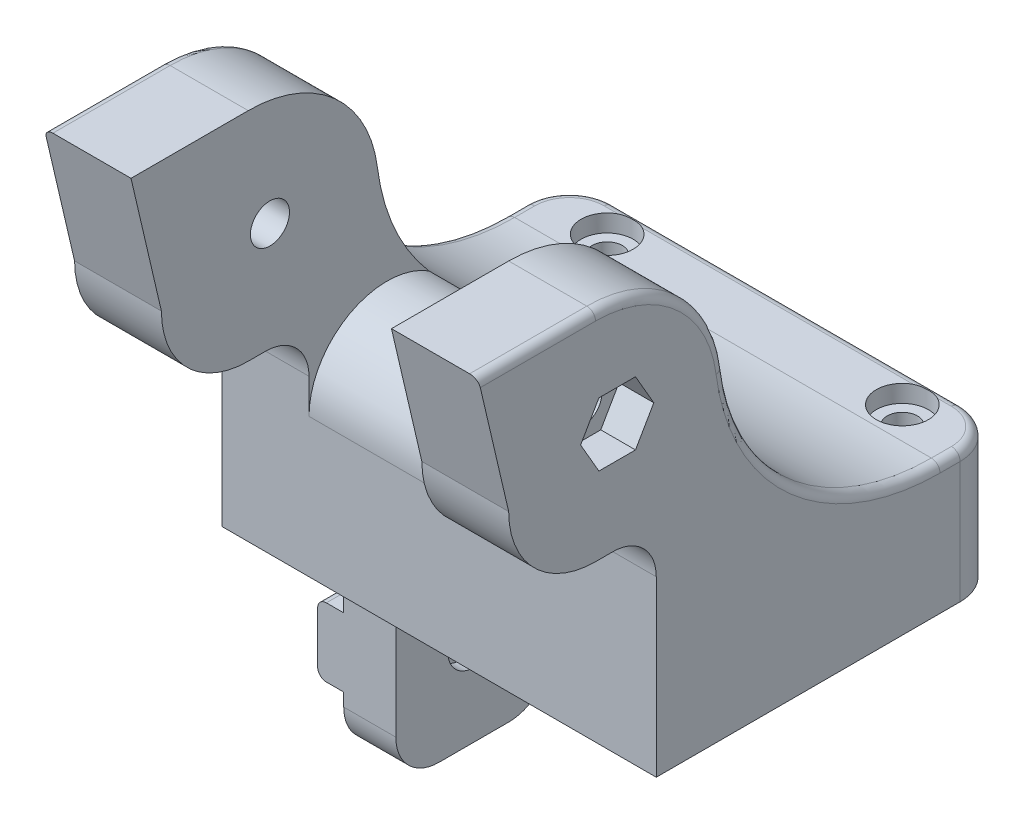
SolidWorks part; units mm, degrees
ref_plane "Alzado" through (0, 0, 0) normal (0, 0, 1) x (1, 0, 0)
ref_plane "Planta" through (0, 0, 0) normal (0, 1, 0) x (1, 0, 0)
ref_plane "Vista lateral" through (0, 0, 0) normal (1, 0, 0) x (0, 0, -1)
sketch "Croquis1" plane through (0, 0, 0) normal (0, 1, 0) x (1, 0, 0)
  line L1 (0, 0) -> (50, 0)
  line L2 (0, 0) -> (0, 40)
  line L3 (0, 40) -> (50, 40)
  line L4 (50, 0) -> (50, 40)
  dimension "D1" = 50
  dimension "D2" = 40
extrude "Saliente-Extruir1" add sketch "Croquis1" along normal blind 25
sketch "Croquis4" plane through (0, 25, 0) normal (0, 1, 0) x (1, 0, 0)
  line L0 (0, 40) -> (0, 0) construction
  line L1 (0, 8) -> (10, 8)
  line L2 (0, 8) -> (0, -17)
  line L3 (0, -17) -> (10, -17)
  line L4 (10, 8) -> (10, -17)
  line L5 (50, 0) -> (50, 40) construction
  line L6 (50, 8) -> (40, 8)
  line L7 (50, 8) -> (50, -17)
  line L8 (50, -17) -> (40, -17)
  line L9 (40, 8) -> (40, -17)
  line L10 (50, 40) -> (0, 40) construction
  dimension "D1" = 10
  dimension "D2" = 10
  dimension "D3" = 25
  dimension "D4" = 25
  dimension "D5" = 32
  dimension "D6" = 32
extrude "Saliente-Extruir3" add sketch "Croquis4" along normal blind 25
sketch "Croquis5" plane through (50, 0, 0) normal (1, 0, 0) x (0, 0, -1)
  line L0 (8, 50) -> (-17, 25) construction
  circle A0 centre (-4.5, 37.5) radius 2.25
  dimension "D1" = 4.5
extrude "Cortar-Extruir2" cut sketch "Croquis5" against normal up to surface (50 mm away) up to face at (0, 25, -7.75)
fillet "Redondeo4" radius 15 2 edges at (5, 50, -8) (45, 50, -8)
fillet "Redondeo5" radius 10 2 edges at (5, 25, 17) (45, 25, 17)
fillet "Redondeo6" radius 9 1 edges at (25, 25, 0)
sketch "Croquis6" plane through (0, 25, 0) normal (0, 1, 0) x (1, 0, 0)
  line L4 (0, 40) -> (0, 9)
  line L5 (0, 9) -> (50, 9)
  line L6 (50, 9) -> (50, 40)
  line L7 (50, 40) -> (0, 40)
  line L8 (0, 40) -> (0, 9)
  line L9 (0, 9) -> (50, 9)
  line L10 (50, 9) -> (50, 40)
  line L11 (50, 40) -> (0, 40)
  dimension "D1" = 0
extrude "Cortar-Extruir3" cut sketch "Croquis6" against normal blind 10
sketch "Croquis7" plane through (0, 0, -9) normal (0, 0, -1) x (-1, 0, 0)
  line L4 (0, 25) -> (-50, 25)
  line L5 (-50, 25) -> (-50, 15)
  line L6 (-50, 15) -> (0, 15)
  line L7 (0, 15) -> (0, 25)
  line L8 (0, 25) -> (-50, 25)
  line L9 (-50, 25) -> (-50, 15)
  line L10 (-50, 15) -> (0, 15)
  line L11 (0, 15) -> (0, 25)
  dimension "D1" = 0
extrude "Cortar-Extruir4" cut sketch "Croquis7" against normal up to surface (1 mm away) up to face at (5, 29.9721, -8)
fillet "Redondeo7" radius 25 1 edges at (25, 15, -8)
fillet "Redondeo8" radius 5 2 edges at (45, 25, 0) (5, 25, 0)
sketch "Croquis8" plane through (0, 15, 0) normal (0, 1, 0) x (1, 0, 0)
  line L0 (0, 36.3431) -> (50, 36.3431) construction
  line L1 (0, 40) -> (0, 32.6863) construction
  line L2 (50, 32.6863) -> (50, 40) construction
  circle A0 centre (8, 36.3431) radius 1.75
  circle A1 centre (42, 36.3431) radius 1.75
  dimension "D1" = 3.5
  dimension "D2" = 3.5
  dimension "D3" = 8
  dimension "D4" = 8
extrude "Cortar-Extruir5" cut sketch "Croquis8" against normal up to surface (15 mm away) up to face at (25, 0, -20)
sketch "Croquis9" plane through (0, 15, 0) normal (0, 1, 0) x (1, 0, 0)
  circle A0 centre (8, 36.3431) radius 3
  circle A1 centre (42, 36.3431) radius 3
  dimension "D1" = 6
  dimension "D2" = 6
extrude "Cortar-Extruir6" cut sketch "Croquis9" against normal blind 2
fillet "Redondeo9" radius 5 2 edges at (0, 7.5, -40) (50, 7.5, -40)
sketch "Croquis10" plane through (0, 0, 0) normal (0, -1, 0) x (1, 0, 0)
  line L0 (0, -35) -> (0, 0) construction
  line L1 (0, -32) -> (6, -32)
  line L2 (0, -32) -> (0, -14)
  line L3 (0, -14) -> (6, -14)
  line L4 (6, -32) -> (6, -14)
  line L5 (45, -40) -> (5, -40) construction
  dimension "D1" = 18
  dimension "D2" = 8
  dimension "D3" = 6
extrude "Saliente-Extruir4" add sketch "Croquis10" along normal blind 30
sketch "Croquis11" plane through (0, 0, 0) normal (-1, 0, 0) x (0, 0, 1)
  line L0 (-32, -30) -> (-32, 0) construction
  line L1 (-32, -23.5) -> (-14, -23.5)
  line L2 (-32, -23.5) -> (-32, -15.6)
  line L3 (-32, -15.6) -> (-14, -15.6)
  line L4 (-14, -23.5) -> (-14, -15.6)
  line L5 (-14, -30) -> (-14, 0) construction
  line L6 (-14, -30) -> (-32, -30) construction
  dimension "D1" = 6.5
  dimension "D2" = 7.9
extrude "Saliente-Extruir5" add sketch "Croquis11" along normal blind 3
fillet "Redondeo10" radius 1 2 edges at (-3, -23.5, -23) (-3, -15.6, -23)
sketch "Croquis12" plane through (-3, 0, 0) normal (-1, 0, 0) x (0, 0, 1)
  line L0 (-32, -19.55) -> (-14, -19.55) construction
  line L1 (-32, -16.6) -> (-32, -22.5) construction
  line L2 (-14, -22.5) -> (-14, -16.6) construction
  line L3 (-23, -22.5) -> (-23, -16.6) construction
  line L4 (-32, -22.5) -> (-14, -22.5) construction
  line L5 (-14, -16.6) -> (-32, -16.6) construction
  circle A0 centre (-23, -19.55) radius 1.75
  dimension "D1" = 3.5
extrude "Cortar-Extruir7" cut sketch "Croquis12" against normal up to surface (9 mm away) up to face at (6, -15, -23)
sketch "Croquis13" plane through (6, 0, 0) normal (1, 0, 0) x (0, 0, -1)
  circle A0 centre (23, -19.55) radius 3
  dimension "D1" = 6
extrude "Cortar-Extruir8" cut sketch "Croquis13" against normal blind 1.5
sketch "Croquis16" plane through (0, 0, 0) normal (0, -1, 0) x (1, 0, 0)
  line L0 (25, -40) -> (25, 0) construction
  line L1 (45, -40) -> (5, -40) construction
  line L2 (0, 0) -> (50, 0) construction
  circle A0 centre (25, -25.3431) radius 1.75
  circle A1 centre (8, -36.3431) radius 1.75 construction
  dimension "D1" = 3.5
  dimension "D2" = 11
extrude "Cortar-Extruir9" cut sketch "Croquis16" against normal through all
ref_plane "Plano1" through (0, 20, 0) normal (0, 1, 0) x (1, 0, 0)
sketch "Croquis17" plane through (0, 20, 0) normal (0, 1, 0) x (1, 0, 0)
  circle A0 centre (25, 25.3431) radius 3
  dimension "D1" = 6
extrude "Cortar-Extruir10" cut sketch "Croquis17" against normal blind 8
fillet "Redondeo11" radius 5 2 edges at (3, -30, -14) (3, -30, -32)
sketch "Croquis18" plane through (0, 0, 0) normal (-1, 0, 0) x (0, 0, 1)
  circle A0 centre (4.5, 37.5) radius 3.55
  dimension "D1" = 7.1
extrude "Cortar-Extruir11" cut sketch "Croquis18" against normal blind 4
sketch "Croquis21" plane through (0, 0, 0) normal (-1, 0, 0) x (0, 0, 1)
  line L0 (17, 50) -> (20.5, 50)
  line L1 (20.5, 50) -> (17, 35)
  line L2 (17, 35) -> (17, 50)
  dimension "D1" = 3.5
extrude "Saliente-Extruir7" add sketch "Croquis21" against normal up to surface (10 mm away) up to face at (10, 37.5, 6.75)
sketch "Croquis23" plane through (50, 0, 0) normal (1, 0, 0) x (0, 0, -1)
  line L0 (-17, 50) -> (-20.5, 50)
  line L1 (-20.5, 50) -> (-17, 35)
  line L2 (-17, 35) -> (-17, 50)
extrude "Saliente-Extruir9" add sketch "Croquis23" against normal up to surface (10 mm away) up to face at (40, 37.5, 2.25)
fillet "Redondeo12" radius 1 11 edges at (0, 50, 13.75) (0, 46.25, -2.9216) (0, 21.25, -16.1503) (0, 15, -33.8431) (1.4645, 15, -38.5355) (25, 15, -40) (48.5355, 15, -38.5355) (50, 15, -33.8431) (50, 50, 13.75) (50, 46.25, -2.9216) (50, 21.25, -16.1503)
sketch "Croquis24" plane through (50, 0, 0) normal (1, 0, 0) x (0, 0, -1)
  line L1 (-2.3927, 33.85) -> (-0.2853, 37.5)
  line L2 (-0.2853, 37.5) -> (-2.3927, 41.15)
  line L3 (-2.3927, 41.15) -> (-6.6073, 41.15)
  line L4 (-6.6073, 41.15) -> (-8.7147, 37.5)
  line L5 (-8.7147, 37.5) -> (-6.6073, 33.85)
  line L6 (-6.6073, 33.85) -> (-2.3927, 33.85)
  line L7 (0, 0) -> (35, 0) construction
  circle A0 centre (-4.5, 37.5) radius 3.65 construction
  dimension "D1" = 7.3
extrude "Cortar-Extruir12" cut sketch "Croquis24" against normal blind 4
